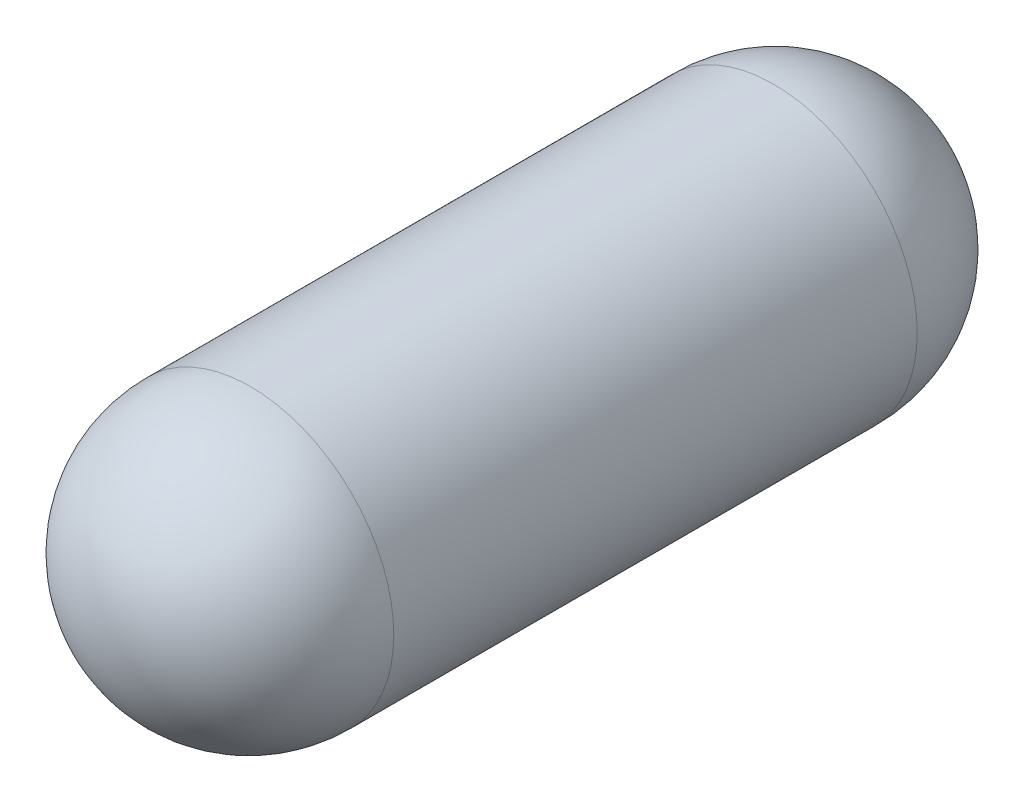
SolidWorks part; units mm, degrees
ref_plane "Front Plane" through (0, 0, 0) normal (0, 0, 1) x (1, 0, 0)
ref_plane "Top Plane" through (0, 0, 0) normal (0, 1, 0) x (1, 0, 0)
ref_plane "Right Plane" through (0, 0, 0) normal (1, 0, 0) x (0, 0, -1)
sketch "Sketch1" plane through (0, 0, 0) normal (0, 0, 1) x (1, 0, 0)
  circle A0 centre (0, 0) radius 48.7362
  dimension "D1" = 97.4725
extrude "Boss-Extrude1" add sketch "Sketch1" along normal blind 177.8
dome "Dome1" faces to dome 1 distance 49.2125 reverse direction no elliptical dome no face at (48.7362, 0, 177.8) parameters "D1"=49.2125
dome "Dome2" faces to dome 1 distance 49.2125 reverse direction no elliptical dome no face at (48.7362, 0, 0) parameters "D1"=49.2125
